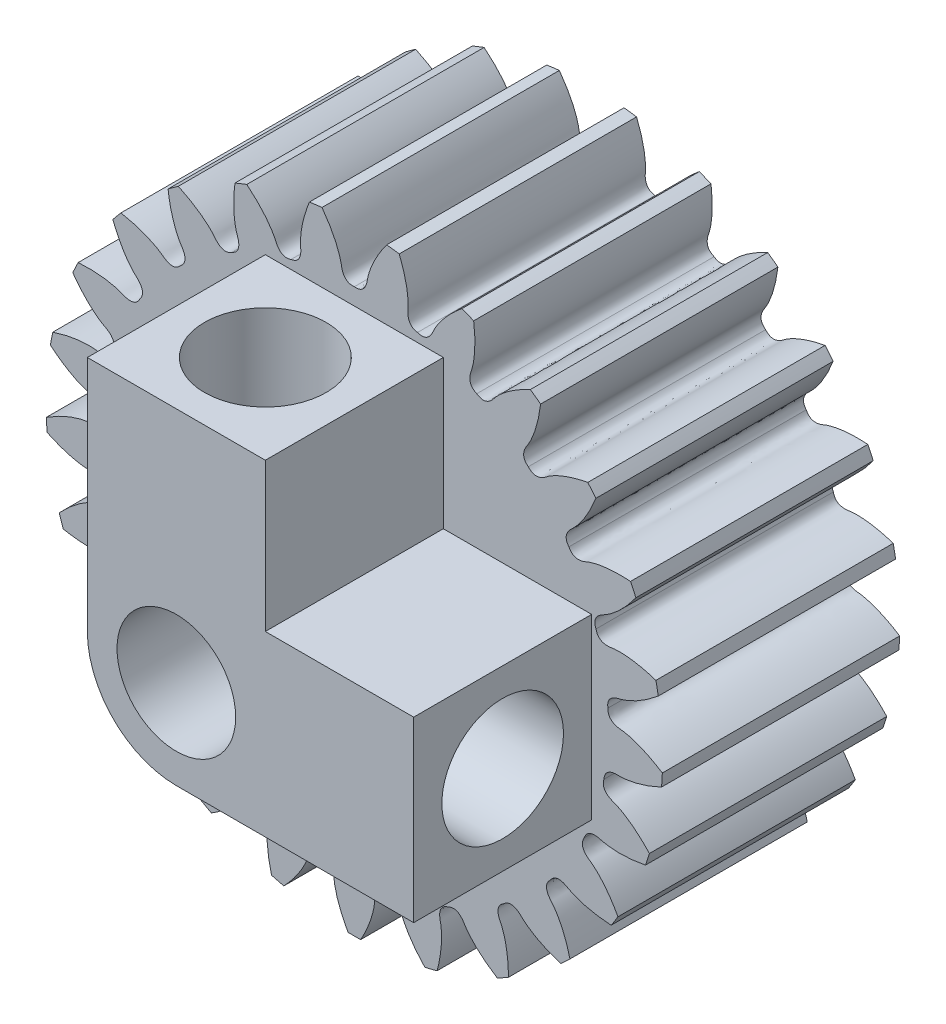
SolidWorks part; units mm, degrees
material "PLA Black"
ref_plane "Front" through (0, 0, 0) normal (0, 0, 1) x (1, 0, 0)
ref_plane "Top" through (0, 0, 0) normal (0, 1, 0) x (1, 0, 0)
ref_plane "Right" through (0, 0, 0) normal (1, 0, 0) x (0, 0, -1)
ref_axis "Axis1" through (0, 0, -80.9) along (0, 0, 1)
sketch "Gear-BaseSketch" plane through (0, 0, 0) normal (0, 0, 1) x (1, 0, 0)
  circle A0 centre (0, 0) radius 10.3909
  dimension "D1" = 20.7818
extrude "33.0 Diametral Pitch, 20.78mm P.D." add sketch "Gear-BaseSketch" along normal mid plane 8
sketch "Tooth-Sketch; Backlash: 0.0000mm" plane through (0, 0, 0) normal (0, 0, 1) x (1, 0, 0)
  line L0 (0, 0) -> (0, 10.3909) construction
  arc A0 (-1.0905, 10.334) -> (1.0905, 10.334) centre (0, -0.094) cw
  circle A1 centre (0, 0) radius 10.3909 construction
  spline S0 degree 3 poles (-1.0905, 10.334) (-1.0138, 10.2299) (-0.9082, 10.0753) (-0.7851, 9.8689) (-0.7088, 9.729) (-0.6442, 9.5985) (-0.5903, 9.4783) (-0.5464, 9.369) (-0.5115, 9.2711) (-0.4845, 9.1851) (-0.4645, 9.1115) (-0.4506, 9.0507) (-0.4416, 9.0039) (-0.4365, 8.9698) (-0.432, 8.9444) (-0.4246, 8.9083) (-0.4122, 8.8596) (-0.3912, 8.7995) (-0.3638, 8.742) (-0.3272, 8.686) (-0.2761, 8.6321) (-0.1724, 8.5642) (-0.0681, 8.5594) (0, 8.5647) knots 0 0 0 0 0.176711 0.2556 0.328177 0.394444 0.454399 0.508044 0.555377 0.596399 0.63111 0.65951 0.681599 0.696189 0.706616 0.716848 0.746535 0.775185 0.80367 0.83335 0.866218 0.904587 1 1 1 1
  spline S1 degree 3 poles (1.0905, 10.334) (1.0138, 10.2299) (0.9082, 10.0753) (0.7851, 9.8689) (0.7088, 9.729) (0.6442, 9.5985) (0.5903, 9.4783) (0.5464, 9.369) (0.5115, 9.2711) (0.4845, 9.1851) (0.4645, 9.1115) (0.4506, 9.0507) (0.4416, 9.0039) (0.4365, 8.9698) (0.432, 8.9444) (0.4246, 8.9083) (0.4122, 8.8596) (0.3912, 8.7995) (0.3638, 8.742) (0.3272, 8.686) (0.2761, 8.6321) (0.1724, 8.5642) (0.0681, 8.5594) (0, 8.5647) knots 0 0 0 0 0.176711 0.2556 0.328177 0.394444 0.454399 0.508044 0.555377 0.596399 0.63111 0.65951 0.681599 0.696189 0.706616 0.716848 0.746535 0.775185 0.80367 0.83335 0.866218 0.904587 1 1 1 1
extrude "Tooth-Cut, Fine Pitch Involute 20 deg" cut sketch "Tooth-Sketch; Backlash: 0.0000mm" against normal through all and the other way through all
pattern_circular "Tooth Pattern, 25 / 25" count 25 over 360 about axis through (0, 0, -80.9) along (0, 0, 1) of "Tooth-Cut, Fine Pitch Involute 20 deg"
sketch "Sketch4" plane through (0, 0, 4) normal (0, 0, 1) x (1, 0, 0)
  circle A0 centre (0, 0) radius 2
  dimension "D1" = 4
extrude "Cut-Extrude2" cut sketch "Sketch4" against normal through all contours A0
sketch "Sketch6" plane through (0, 0, 4) normal (0, 0, 1) x (1, 0, 0)
  circle A0 centre (0, 0) radius 3
  circle A1 centre (0, 0) radius 2
  circle A2 centre (0, 0) radius 2 construction
  dimension "D1" = 6
extrude "Boss-Extrude2" add sketch "Sketch6" along normal blind 6
sketch "Sketch9" plane through (0, 0, 4) normal (0, 0, 1) x (1, 0, 0)
  line L0 (-3, 0) -> (-3, 8)
  line L1 (-3, 8) -> (3, 8)
  line L2 (3, 8) -> (3, 3)
  line L3 (3, 3) -> (8, 3)
  line L4 (8, 3) -> (8, -3)
  line L5 (8, -3) -> (0, -3)
  circle A0 centre (0, 0) radius 3 construction
  circle A1 centre (0, 0) radius 3 construction
  arc A2 (-3, 0) -> (0, -3) centre (0, 0) cw
  dimension "D1" = 5
extrude "Boss-Extrude4" add sketch "Sketch9" along normal through all
ref_plane "Plane1" through (0, 3, 0) normal (0, 1, 0) x (1, 0, 0)
sketch "Sketch10" plane through (0, 8, 0) normal (0, 1, 0) x (1, 0, 0)
  line L0 (-3, -7) -> (3, -7) construction
  line L1 (-3, -10) -> (-3, -4) construction
  line L2 (3, -10) -> (3, -4) construction
  line L3 (0, -4) -> (0, -10) construction
  line L4 (3, -10) -> (-3, -10) construction
  circle A0 centre (0, -7) radius 2.05
  dimension "D1" = 4.1
extrude "Cut-Extrude3" cut sketch "Sketch10" against normal blind 8
sketch "Sketch11" plane through (8, 0, 0) normal (1, 0, 0) x (0, 0, -1)
  line L0 (-7, 3) -> (-7, -3) construction
  line L1 (-10, 3) -> (-4, 3) construction
  line L2 (-10, -3) -> (-4, -3) construction
  line L3 (-10, 0) -> (-4, 0) construction
  line L4 (-10, -3) -> (-10, 3) construction
  line L7 (-4, -3) -> (-4, 3) construction
  circle A0 centre (-7, 0) radius 2.05
  dimension "D1" = 4.1
extrude "Cut-Extrude4" cut sketch "Sketch11" against normal blind 8 contours A0
